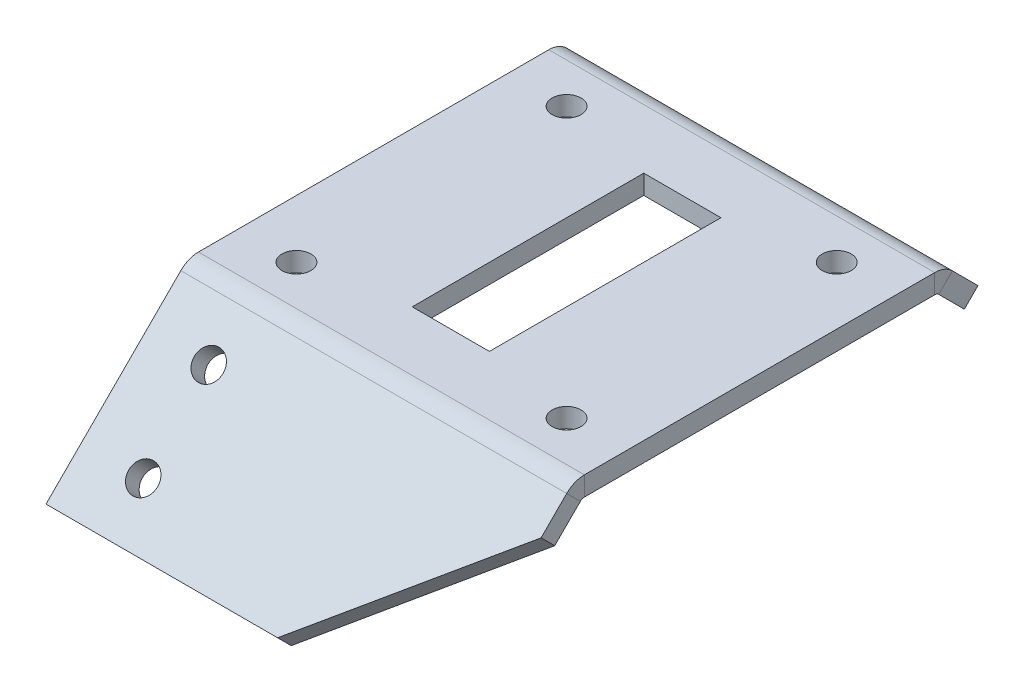
SolidWorks part; units mm, degrees
note: The reader was unsure of these and kept them because the rebuilt part matched: thickness of "Base-Flange1", "Edge-Flange1", "Sheet-Metal1", "Sheet-Metal2", "Sheet-Metal3", "Sheet-Metal4", "Sheet-Metal5", "Sheet-Metal6"; flange length of "Edge-Flange1".
material "6061 Alloy"
ref_plane "Front Plane" through (0, 0, 0) normal (0, 0, 1) x (1, 0, 0)
ref_plane "Top Plane" through (0, 0, 0) normal (0, 1, 0) x (1, 0, 0)
ref_plane "Right Plane" through (0, 0, 0) normal (1, 0, 0) x (0, 0, -1)
sketch "Sketch1" plane through (0, 0, 0) normal (0, 1, 0) x (1, 0, 0)
  line L0 (0, -23) -> (0, 23)
  line L1 (0, -23) -> (50, -23)
  line L2 (0, 23) -> (50, 23)
  line L3 (50, -23) -> (50, 23)
  point P0 (0, 0)
  dimension "D1" = 50
  dimension "D2" = 46
base flange "Base-Flange1" sketch "Sketch1" thickness 2.5 reverse thickness direction yes parameters "D1"=0.7366
edge flange "Edge-Flange1" sketch "Sketch10" flange profiles "Sketch10", "Sketch12" flange angle 135 flange length 25 flange position material outside bend radius 0.7366 thickness 2.5 relief rectangular parameters "D6"=10, "D8"=1
sketch "Sketch10" plane through (0, 0, -23) normal (0, 0.7071, -0.7071) x (1, 0, 0)
  line L2 (0, 0) -> (0, 25)
  line L3 (0, 25) -> (50, 25)
  line L4 (50, 25) -> (50, 0)
  line L11 (50, 0) -> (0, 0) construction
  line L12 (50, 0) -> (0, 0)
sketch "Sketch12" plane through (0, 0, 23) normal (0, 0.7071, 0.7071) x (-1, 0, 0)
  line L0 (0, 0) -> (-50, 0) construction
  line L1 (0, 0) -> (-50, 0)
  line L2 (-50, 0) -> (-50, 25)
  line L3 (-50, 25) -> (0, 25)
  line L4 (0, 25) -> (0, 0)
bend "EdgeBend1" bend radius 0.7366 bend angle 45 parameters "D5"=1
bend "EdgeBend2" bend radius 0.7366 bend angle 45 parameters "D5"=3
sketch "Sketch13" plane through (0, 13.2678, 13.2678) normal (0, 0.7071, 0.7071) x (1, 0, 0)
  line L0 (0, -41.2635) -> (50, -41.2635) construction
  line L1 (0, -16.5686) -> (0, -41.2635) construction
  circle A0 centre (8, -22.7635) radius 1.875
  circle A1 centre (8, -34.7635) radius 1.875
  dimension "D1" = 3.75
  dimension "D2" = 12
  dimension "D3" = 6.5
  dimension "D4" = 8
extrude "Cut-Extrude1" cut sketch "Sketch13" against normal up to next normal cut yes
mirror "Mirror1" about plane through (0, 0, 0) normal (0, 0, 1) of "Cut-Extrude1"
sketch "Sketch14" plane through (0, 2.5, 0) normal (0, 1, 0) x (1, 0, 0)
  line L0 (0, 22.6949) -> (0, -22.6949) construction
  line L1 (7.5, 17.5) -> (42.5, 17.5) construction
  line L2 (7.5, 17.5) -> (7.5, -17.5) construction
  line L3 (7.5, -17.5) -> (42.5, -17.5) construction
  line L4 (42.5, 17.5) -> (42.5, -17.5) construction
  circle A0 centre (7.5, 17.5) radius 1.875
  circle A1 centre (42.5, 17.5) radius 1.875
  circle A2 centre (7.5, -17.5) radius 1.875
  circle A3 centre (42.5, -17.5) radius 1.875
  point P15 (7.5, 0)
  dimension "D1" = 35
  dimension "D3" = 3.75
  dimension "D2" = 35
  dimension "D4" = 7.5
extrude "Cut-Extrude2" cut sketch "Sketch14" against normal up to next normal cut yes
chamfer "Chamfer1" distance 20 angle 45 2 edges at (50, -16.7938, -41.5616) (50, -16.7938, 41.5616)
sketch "Sketch15" plane through (0, 2.5, 0) normal (0, 1, 0) x (1, 0, 0)
  line L0 (0, 22.6949) -> (0, -22.6949) construction
  line L1 (20, 15) -> (30, 15)
  line L2 (20, 15) -> (20, -15)
  line L3 (20, -15) -> (30, -15)
  line L4 (30, 15) -> (30, -15)
  point P4 (20, 0)
  dimension "D1" = 10
  dimension "D2" = 30
  dimension "D3" = 20
extrude "Cut-Extrude3" cut sketch "Sketch15" against normal up to next normal cut yes
sketch "Bend-Lines1" [suppressed] plane through (0, 0, 0) normal (0, 1, 0) x (1, 0, 0)
sketch "Bounding-Box1" [suppressed] plane through (0, 0, 0) normal (0, 1, 0) x (1, 0, 0)
sheet metal parameters "Sheet-Metal1" thickness 2.5 parameters "D1"=0.7366
flat pattern "Flat-Pattern1" [suppressed]
sketch "Bend-Lines2" plane through (0, 0, 0) normal (0, 1, 0) x (1, 0, 0)
sketch3d "Bounding-Box2" [suppressed]
  line L0 (-50, -23, 0) -> (0, -23, 0) construction
  line L1 (-50, 23, 0) -> (0, 23, 0) construction
  line L2 (-50, -23, 0) -> (-50, 23, 0) construction
  line L3 (0, -23, 0) -> (0, 23, 0) construction
sheet metal parameters "Sheet-Metal2" thickness 2.5 parameters "D1"=0.7366, "D7"=0.7366
flat pattern "Flat-Pattern1"
sketch "Bend-Lines2" plane through (0, 0, 0) normal (0, -1, 0) x (-1, 0, 0)
  line L0 (0, 23.1288) -> (-50, 23.1288) construction
  line L1 (0, 23.1288) -> (-50, 23.1288) construction
  line L2 (-50, -23.1288) -> (0, -23.1288) construction
  line L3 (-50, -23.1288) -> (0, -23.1288) construction
sketch3d "Bounding-Box2" [suppressed]
  line L0 (0, 48.2576, 0) -> (0, -48.2576, 0) construction
  line L1 (-50, 48.2576, 0) -> (-50, -48.2576, 0) construction
  line L2 (0, 48.2576, 0) -> (-50, 48.2576, 0) construction
  line L3 (0, -48.2576, 0) -> (-50, -48.2576, 0) construction
bend of the flat pattern "Flatten-<EdgeBend1>1"
bend of the flat pattern "Flatten-<EdgeBend2>1"
sheet metal parameters "Sheet-Metal3" thickness 2.5 parameters "D1"=0.7366, "D7"=0.7366
flat pattern "Flat-Pattern1"
sketch "Bend-Lines2" plane through (0, 0, 0) normal (0, -1, 0) x (-1, 0, 0)
  line L0 (0, 23.1288) -> (-50, 23.1288) construction
  line L1 (0, 23.1288) -> (-50, 23.1288) construction
  line L2 (-50, -23.1288) -> (0, -23.1288) construction
  line L3 (-50, -23.1288) -> (0, -23.1288) construction
sketch3d "Bounding-Box2" [suppressed]
  line L0 (0, 48.2576, 0) -> (0, -48.2576, 0) construction
  line L1 (-50, 48.2576, 0) -> (-50, -48.2576, 0) construction
  line L2 (0, 48.2576, 0) -> (-50, 48.2576, 0) construction
  line L3 (0, -48.2576, 0) -> (-50, -48.2576, 0) construction
bend of the flat pattern "Flatten-<EdgeBend1>1"
bend of the flat pattern "Flatten-<EdgeBend2>1"
sheet metal parameters "Sheet-Metal4" thickness 2.5 parameters "D1"=0.7366, "D7"=0.7366
flat pattern "Flat-Pattern1"
sketch "Bend-Lines2" plane through (0, 0, 0) normal (0, -1, 0) x (-1, 0, 0)
  line L0 (0, 23.1288) -> (-50, 23.1288) construction
  line L1 (0, 23.1288) -> (-50, 23.1288) construction
  line L2 (-50, -23.1288) -> (0, -23.1288) construction
  line L3 (-50, -23.1288) -> (0, -23.1288) construction
sketch3d "Bounding-Box2" [suppressed]
  line L0 (0, 48.2576, 0) -> (0, -48.2576, 0) construction
  line L1 (-50, 48.2576, 0) -> (-50, -48.2576, 0) construction
  line L2 (0, 48.2576, 0) -> (-50, 48.2576, 0) construction
  line L3 (0, -48.2576, 0) -> (-50, -48.2576, 0) construction
bend of the flat pattern "Flatten-<EdgeBend1>1"
bend of the flat pattern "Flatten-<EdgeBend2>1"
sheet metal parameters "Sheet-Metal5" thickness 2.5 parameters "D1"=0.7366, "D7"=0.7366
flat pattern "Flat-Pattern1"
sketch "Bend-Lines2" plane through (0, 0, 0) normal (0, -1, 0) x (-1, 0, 0)
  line L0 (0, 23.1288) -> (-50, 23.1288) construction
  line L1 (0, 23.1288) -> (-50, 23.1288) construction
  line L2 (-50, -23.1288) -> (0, -23.1288) construction
  line L3 (-50, -23.1288) -> (0, -23.1288) construction
sketch3d "Bounding-Box2" [suppressed]
  line L0 (0, 48.2576, 0) -> (0, -48.2576, 0) construction
  line L1 (-50, 48.2576, 0) -> (-50, -48.2576, 0) construction
  line L2 (0, 48.2576, 0) -> (-50, 48.2576, 0) construction
  line L3 (0, -48.2576, 0) -> (-50, -48.2576, 0) construction
bend of the flat pattern "Flatten-<EdgeBend1>1"
bend of the flat pattern "Flatten-<EdgeBend2>1"
sheet metal parameters "Sheet-Metal6" thickness 2.5 parameters "D1"=0.7366, "D7"=0.7366
flat pattern "Flat-Pattern1"
sketch "Bend-Lines2" plane through (0, 0, 0) normal (0, -1, 0) x (-1, 0, 0)
  line L0 (0, 23.475) -> (-50, 23.475) construction
  line L1 (0, 23.475) -> (-50, 23.475) construction
  line L2 (-50, -23.475) -> (0, -23.475) construction
  line L3 (-50, -23.475) -> (0, -23.475) construction
sketch3d "Bounding-Box2" [suppressed]
  line L0 (0, 48.9501, 0) -> (0, -48.9501, 0) construction
  line L1 (-50, 48.9501, 0) -> (-50, -48.9501, 0) construction
  line L2 (0, 48.9501, 0) -> (-50, 48.9501, 0) construction
  line L3 (0, -48.9501, 0) -> (-50, -48.9501, 0) construction
bend of the flat pattern "Flatten-<EdgeBend1>1"
bend of the flat pattern "Flatten-<EdgeBend2>1"
